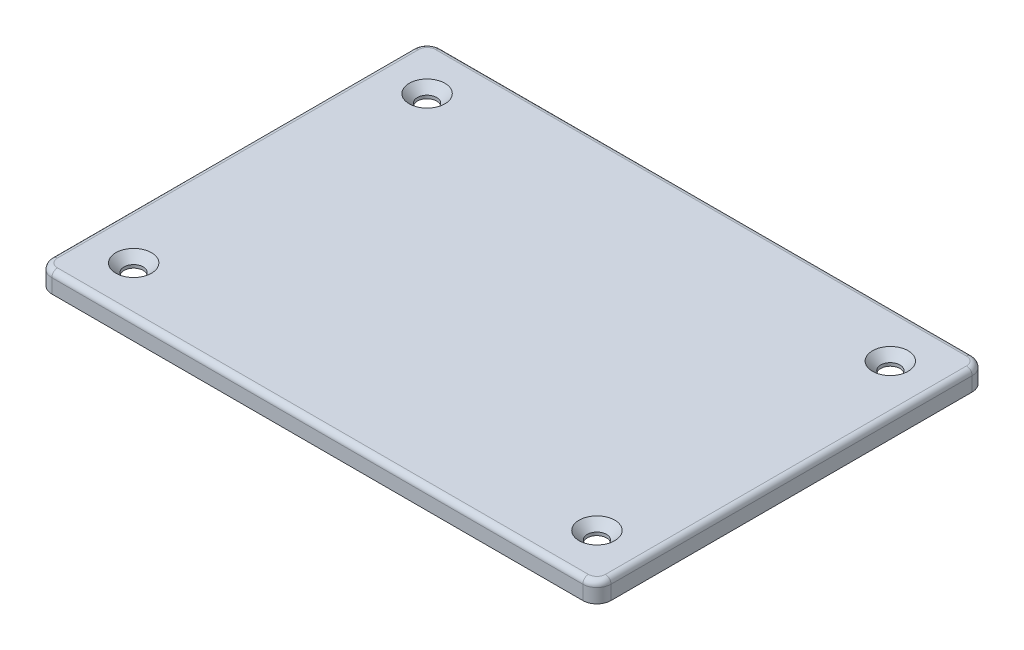
SolidWorks part; units mm, degrees
ref_plane "Front Plane" through (0, 0, 0) normal (0, 0, 1) x (1, 0, 0)
ref_plane "Top Plane" through (0, 0, 0) normal (0, 1, 0) x (1, 0, 0)
ref_plane "Right Plane" through (0, 0, 0) normal (1, 0, 0) x (0, 0, -1)
sketch "Sketch2" plane through (0, 0, 0) normal (0, 1, 0) x (1, 0, 0)
  line L1 (49.3891, -34.3891) -> (-49.3891, -34.3891)
  line L2 (49.3891, -34.3891) -> (49.3891, 34.3891)
  line L3 (49.3891, 34.3891) -> (-49.3891, 34.3891)
  line L4 (-49.3891, -34.3891) -> (-49.3891, 34.3891)
  line L5 (49.3891, -34.3891) -> (-49.3891, 34.3891) construction
  line L6 (49.3891, 34.3891) -> (-49.3891, -34.3891) construction
  point P0 (0, 0)
  dimension "D1" = 98.7781
  dimension "D2" = 68.7781
extrude "Boss-Extrude1" add sketch "Sketch2" along normal blind 3.5
fillet "Fillet1" radius 1 4 edges at (0, 3.5, -34.3891) (49.3891, 3.5, 0) (0, 3.5, 34.3891) (-49.3891, 3.5, 0)
fillet "Fillet2" radius 2.5 8 edges at (49.0962, 3.2071, -34.0962) (-49.0962, 3.2071, -34.0962) (-49.0962, 3.2071, 34.0962) (49.0962, 3.2071, 34.0962) (49.3891, 1.25, 34.3891) (-49.3891, 1.25, 34.3891) (-49.3891, 1.25, -34.3891) (49.3891, 1.25, -34.3891)
sketch "Sketch3" plane through (0, 0, 0) normal (0, -1, 0) x (1, 0, 0)
  line L12 (47.8891, -31.8891) -> (47.8891, 31.8891)
  line L13 (46.8891, 32.8891) -> (-46.8891, 32.8891)
  line L14 (-47.8891, 31.8891) -> (-47.8891, -31.8891)
  line L15 (-46.8891, -32.8891) -> (46.8891, -32.8891)
  line L16 (47.8891, -31.8891) -> (47.8891, 31.8891)
  line L17 (46.8891, 32.8891) -> (-46.8891, 32.8891)
  line L18 (-47.8891, 31.8891) -> (-47.8891, -31.8891)
  line L19 (-46.8891, -32.8891) -> (46.8891, -32.8891)
  arc A12 (47.8891, 31.8891) -> (46.8891, 32.8891) centre (46.8891, 31.8891) ccw
  arc A13 (-46.8891, 32.8891) -> (-47.8891, 31.8891) centre (-46.8891, 31.8891) ccw
  arc A14 (-47.8891, -31.8891) -> (-46.8891, -32.8891) centre (-46.8891, -31.8891) ccw
  arc A15 (46.8891, -32.8891) -> (47.8891, -31.8891) centre (46.8891, -31.8891) ccw
  arc A16 (47.8891, 31.8891) -> (46.8891, 32.8891) centre (46.8891, 31.8891) ccw
  arc A17 (-46.8891, 32.8891) -> (-47.8891, 31.8891) centre (-46.8891, 31.8891) ccw
  arc A18 (-47.8891, -31.8891) -> (-46.8891, -32.8891) centre (-46.8891, -31.8891) ccw
  arc A19 (46.8891, -32.8891) -> (47.8891, -31.8891) centre (46.8891, -31.8891) ccw
  dimension "D1" = 1.5
extrude "Cut-Extrude1" cut sketch "Sketch3" against normal blind 1.5
sketch "Sketch4" plane through (0, 3.5, 0) normal (0, 1, 0) x (1, 0, 0)
  line L0 (46.8891, 33.3891) -> (-46.8891, 33.3891) construction
  line L1 (-48.3891, 31.8891) -> (-48.3891, -31.8891) construction
  line L2 (48.3891, -31.8891) -> (48.3891, 31.8891) construction
  line L3 (-46.8891, -33.3891) -> (46.8891, -33.3891) construction
  circle A0 centre (-40.912, 25.912) radius 1.5
  circle A1 centre (40.912, 25.912) radius 1.5
  circle A2 centre (40.912, -25.912) radius 1.5
  circle A3 centre (-40.912, -25.912) radius 1.5
  point P12 (0, 0)
  point P13 (0, 0)
  point P14 (0, 0)
  point P15 (0, 0)
  dimension "D1" = 3
  dimension "D2" = 7.4771
  dimension "D3" = 7.4771
  dimension "D4" = 7.4771
  dimension "D5" = 7.4771
  dimension "D6" = 7.4771
  dimension "D7" = 7.4771
  dimension "D8" = 7.4771
  dimension "D9" = 7.4771
hole_wizard "CSK for M3 Countersunk Flat Head Screw1" positions "3DSketch1" profile "Sketch5" countersink size "M3" standard "ISO"
sketch3d "3DSketch1"
  point P0 (-40.912, 3.5, -25.912)
  point P3 (40.912, 3.5, -25.912)
  point P6 (40.912, 3.5, 25.912)
  point P9 (-40.912, 3.5, 25.912)
sketch "Sketch5" plane through (-40.912, 3.5, -25.912) normal (1, 0, 0) x (0, 0, 1)
  line L0 (0, 0) -> (0, 11.0215)
  line L1 (0, 11.0215) -> (1.7, 10)
  line L2 (1.7, 10) -> (1.7, 1.45)
  line L3 (1.7, 1.45) -> (3.15, 0)
  line L5 (3.15, 0) -> (0, 0)
  line L6 (-1.7, 1.45) -> (-3.15, 0) construction
  line L10 (0, 11.0215) -> (-1.7, 10) construction
  line L11 (0, -6.35) -> (0, 107.95) construction
  dimension "Hole Dia." = 3.4
  dimension "Hole Depth" = 10
  dimension "Near C'Sink Dia." = 6.3
  dimension "Near C'Sink Angle" = 90
  dimension "Drill Angle" = 118
